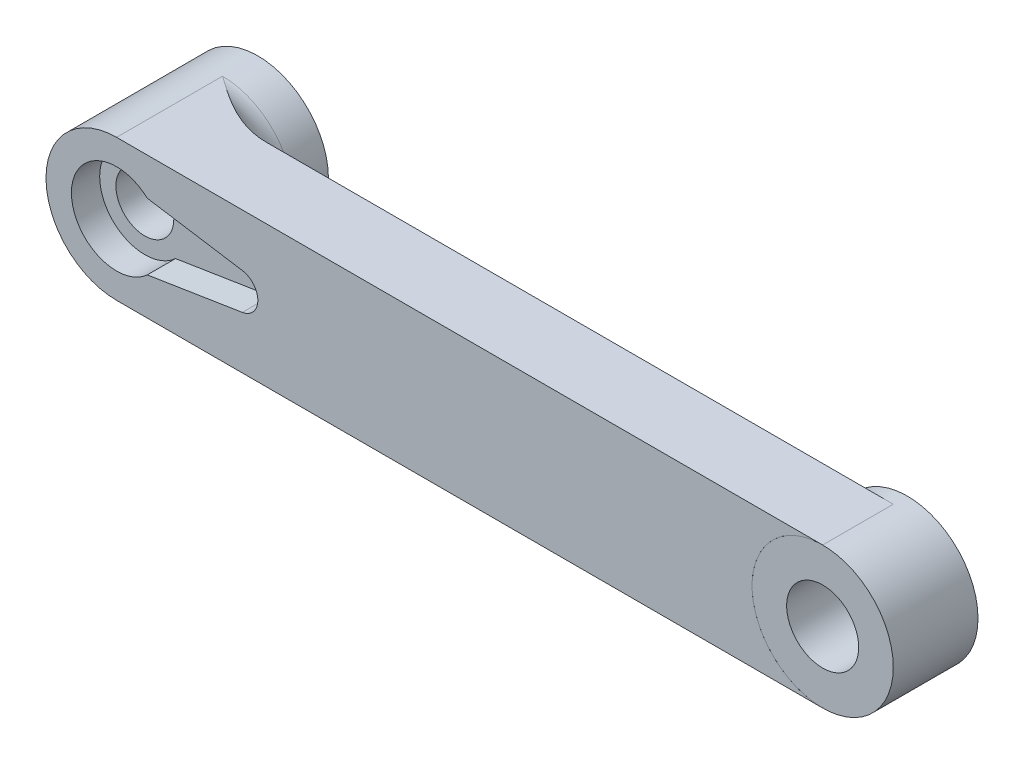
SolidWorks part; units mm, degrees
note: The reader was unsure of these and kept them because the rebuilt part matched: shared geometry of "Эскиз1<4>", "Эскиз1<3>".
ref_plane "Спереди" through (0, 0, 0) normal (0, 0, 1) x (1, 0, 0)
ref_plane "Сверху" through (0, 0, 0) normal (0, 1, 0) x (1, 0, 0)
ref_plane "Справа" through (0, 0, 0) normal (1, 0, 0) x (0, 0, -1)
sketch "Эскиз1" plane through (0, 0, 0) normal (0, 0, 1) x (1, 0, 0)
  line L0 (0, 10) -> (100, 10)
  line L1 (0, 0) -> (100, 0) construction
  line L2 (0, -10) -> (100, -10)
  circle A0 centre (0, 0) radius 4.1
  circle A1 centre (0, 0) radius 10
  circle A2 centre (100, 0) radius 5.1
  circle A3 centre (100, 0) radius 10
  dimension "D1" = 8.2
  dimension "D2" = 20
  dimension "D4" = 20
  dimension "D5" = 10.2
  dimension "D3" = 100
extrude "Бобышка-Вытянуть1" add sketch "Эскиз1" against normal blind 20
extrude "Бобышка-под втулку" add sketch "Эскиз1<4>" against normal blind 12
sketch "Эскиз1<4>" plane through (0, 0, 0) normal (0, 0, 1) x (1, 0, 0) same geometry as "Эскиз1"
extrude "Бобышка-Вытянуть2" add sketch "Эскиз1<3>" against normal blind 10 contours A1 L1 A3 L0 | L1 A1 L2 A3
sketch "Эскиз1<3>" plane through (0, 0, 0) normal (0, 0, 1) x (1, 0, 0) same geometry as "Эскиз1"
sketch "Эскиз2" plane through (0, 0, 0) normal (0, 0, 1) x (1, 0, 0)
  line L0 (0, 0) -> (17.4, 0) construction
  line L1 (4.3436, 4.7003) -> (17.8067, 2.568)
  line L2 (4.3436, -4.7003) -> (17.8067, -2.568)
  circle A0 centre (0, 0) radius 6.4
  circle A1 centre (17.4, 0) radius 2.6
  dimension "D2" = 12.8
  dimension "D3" = 5.2
  dimension "D1" = 17.4
  dimension "D4" = 18
extrude "Вырез-носик сервы" cut sketch "Эскиз2" against normal blind 4
chamfer "Фаска1" distance 1 angle 45 1 edges at (4.1, 0, -20)
fillet "Скругление1" radius 5 1 edges at (10, 0, -10)
